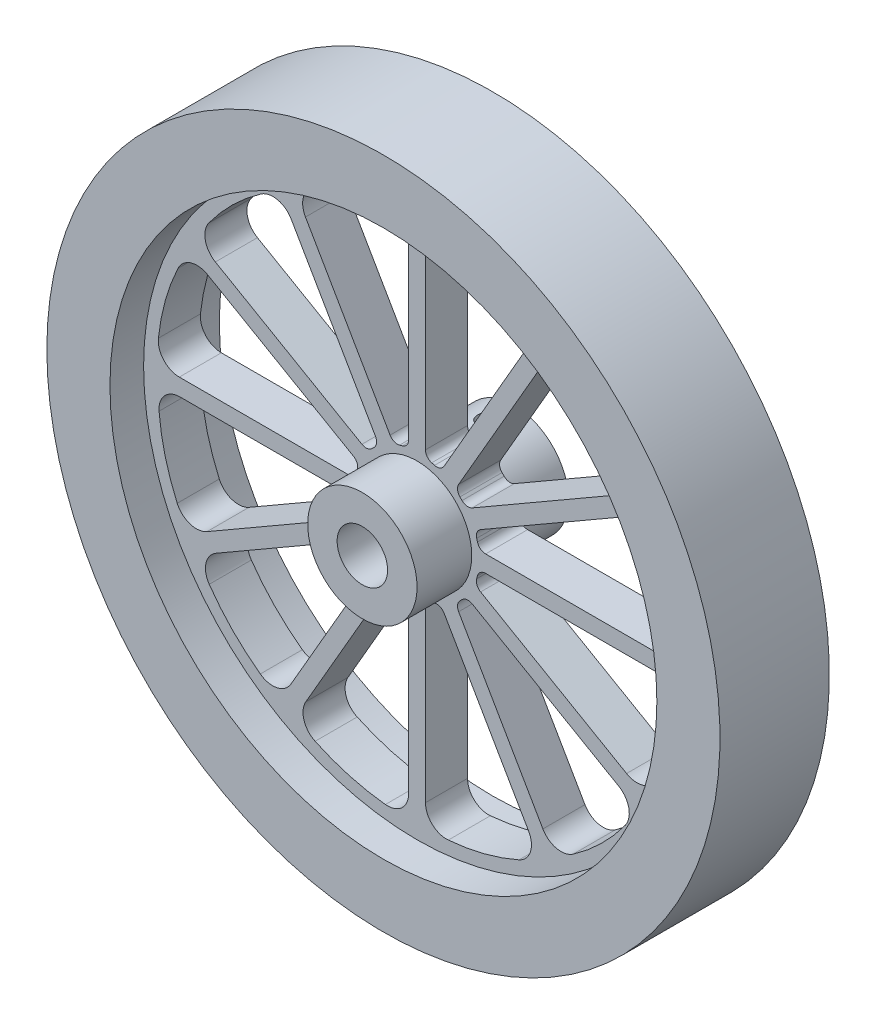
SolidWorks part; units mm, degrees
ref_plane "Front Plane" through (0, 0, 0) normal (0, 0, 1) x (1, 0, 0)
ref_plane "Top Plane" through (0, 0, 0) normal (0, 1, 0) x (1, 0, 0)
ref_plane "Right Plane" through (0, 0, 0) normal (1, 0, 0) x (0, 0, -1)
sketch "Sketch1" plane through (0, 0, 0) normal (0, 0, 1) x (1, 0, 0)
  line L0 (0, 93.8626) -> (0, -13) construction
  line L1 (2, 16.2894) -> (2, 56.5143)
  line L2 (9.8767, 13.107) -> (29.9892, 47.9429)
  line L3 (9.6149, 12.6535) -> (9.8767, 13.107)
  line L4 (6.4126, 15.107) -> (26.4422, 49.7992)
  line L5 (10.1946, 10.6928) -> (10.6928, 10.1946)
  line L6 (13.107, 9.8767) -> (47.7992, 29.9063)
  line L7 (15.107, 6.4126) -> (49.9429, 26.5251)
  line L8 (14.1752, 4.1629) -> (14.3575, 3.4824)
  line L9 (16.2894, 2) -> (56.3484, 2)
  line L10 (16.2894, -2) -> (56.5143, -2)
  line L11 (14.3575, -3.4824) -> (14.1752, -4.1629)
  line L12 (15.107, -6.4126) -> (49.7992, -26.4422)
  line L13 (13.107, -9.8767) -> (47.9429, -29.9892)
  line L14 (10.6928, -10.1946) -> (10.1946, -10.6928)
  line L15 (9.8767, -13.107) -> (29.9063, -47.7992)
  line L16 (6.4126, -15.107) -> (26.5251, -49.9429)
  line L17 (4.1629, -14.1752) -> (3.4824, -14.3575)
  line L18 (2, -16.2894) -> (2, -56.3484)
  line L19 (-2, -16.2894) -> (-2, -56.5143)
  line L20 (-3.4824, -14.3575) -> (-4.1629, -14.1752)
  line L21 (0, -65) -> (0, -93.8626) construction
  line L22 (-6.4126, -15.107) -> (-26.4422, -49.7992)
  line L23 (-9.8767, -13.107) -> (-29.9892, -47.9429)
  line L24 (-10.1946, -10.6928) -> (-10.6928, -10.1946)
  line L25 (3.4824, 14.3575) -> (4.1629, 14.1752)
  line L26 (-13.107, -9.8767) -> (-47.7992, -29.9063)
  line L27 (-15.107, -6.4126) -> (-49.9429, -26.5251)
  line L28 (-14.1752, -4.1629) -> (-14.3575, -3.4824)
  line L29 (-16.2894, -2) -> (-56.3484, -2)
  line L30 (-16.2894, 2) -> (-56.5143, 2)
  line L31 (-14.3575, 3.4824) -> (-14.1752, 4.1629)
  line L32 (-15.107, 6.4126) -> (-49.7992, 26.4422)
  line L33 (-13.107, 9.8767) -> (-47.9429, 29.9892)
  line L34 (-10.6928, 10.1946) -> (-10.1946, 10.6928)
  line L35 (-9.8767, 13.107) -> (-29.9063, 47.7992)
  line L36 (-6.4126, 15.107) -> (-26.5251, 49.9429)
  line L37 (-4.1629, 14.1752) -> (-3.4824, 14.3575)
  line L38 (-2, 16.2894) -> (-2, 56.3484)
  line L39 (0, 0) -> (2, 9.3915) construction
  circle A0 centre (0, 0) radius 65
  circle A1 centre (0, 0) radius 80
  circle A2 centre (0, 0) radius 6
  circle A3 centre (0, 0) radius 13
  arc A4 (7.5276, 61.4864) -> (24.2341, 56.8265) centre (2, 9.3915) cw
  arc A6 (26.4422, 49.7992) -> (24.2341, 56.8265) centre (22.112, 52.2992) ccw
  arc A7 (2, 56.5143) -> (7.5276, 61.4864) centre (7, 56.5143) cw
  arc A9 (6.4126, 15.107) -> (4.1629, 14.1752) centre (4.6806, 16.107) cw
  arc A10 (2, 16.2894) -> (3.4824, 14.3575) centre (4, 16.2894) ccw
  arc A11 (9.8767, 13.107) -> (10.1946, 10.6928) centre (11.6088, 12.107) ccw
  arc A12 (13.107, 9.8767) -> (10.6928, 10.1946) centre (12.107, 11.6088) cw
  arc A13 (47.7992, 29.9063) -> (49.4006, 37.0961) centre (45.2992, 34.2364) ccw
  arc A14 (37.2623, 49.485) -> (49.4006, 37.0961) centre (6.4278, 7.1333) cw
  arc A15 (29.9892, 47.9429) -> (37.2623, 49.485) centre (34.3193, 45.4429) cw
  arc A16 (15.107, 6.4126) -> (14.1752, 4.1629) centre (16.107, 4.6806) ccw
  arc A17 (16.2894, 2) -> (14.3575, 3.4824) centre (16.2894, 4) cw
  arc A18 (56.3484, 2) -> (61.3303, 7.4259) centre (56.3484, 7) ccw
  arc A19 (57.0126, 24.2242) -> (61.3303, 7.4259) centre (9.1333, 2.9637) cw
  arc A20 (49.9429, 26.5251) -> (57.0126, 24.2242) centre (52.4429, 22.195) cw
  arc A21 (16.2894, -2) -> (14.3575, -3.4824) centre (16.2894, -4) ccw
  arc A22 (15.107, -6.4126) -> (14.1752, -4.1629) centre (16.107, -4.6806) cw
  arc A23 (49.7992, -26.4422) -> (56.8265, -24.2341) centre (52.2992, -22.112) ccw
  arc A24 (61.4864, -7.5276) -> (56.8265, -24.2341) centre (9.3915, -2) cw
  arc A25 (56.5143, -2) -> (61.4864, -7.5276) centre (56.5143, -7) cw
  arc A26 (13.107, -9.8767) -> (10.6928, -10.1946) centre (12.107, -11.6088) ccw
  arc A27 (9.8767, -13.107) -> (10.1946, -10.6928) centre (11.6088, -12.107) cw
  arc A28 (29.9063, -47.7992) -> (37.0961, -49.4006) centre (34.2364, -45.2992) ccw
  arc A29 (49.485, -37.2623) -> (37.0961, -49.4006) centre (7.1333, -6.4278) cw
  arc A30 (47.9429, -29.9892) -> (49.485, -37.2623) centre (45.4429, -34.3193) cw
  arc A31 (6.4126, -15.107) -> (4.1629, -14.1752) centre (4.6806, -16.107) ccw
  arc A32 (2, -16.2894) -> (3.4824, -14.3575) centre (4, -16.2894) cw
  arc A33 (2, -56.3484) -> (7.4259, -61.3303) centre (7, -56.3484) ccw
  arc A34 (24.2242, -57.0126) -> (7.4259, -61.3303) centre (2.9637, -9.1333) cw
  arc A35 (26.5251, -49.9429) -> (24.2242, -57.0126) centre (22.195, -52.4429) cw
  arc A36 (-2, -16.2894) -> (-3.4824, -14.3575) centre (-4, -16.2894) ccw
  arc A37 (-6.4126, -15.107) -> (-4.1629, -14.1752) centre (-4.6806, -16.107) cw
  arc A38 (-26.4422, -49.7992) -> (-24.2341, -56.8265) centre (-22.112, -52.2992) ccw
  arc A39 (-7.5276, -61.4864) -> (-24.2341, -56.8265) centre (-2, -9.3915) cw
  arc A40 (-2, -56.5143) -> (-7.5276, -61.4864) centre (-7, -56.5143) cw
  arc A41 (-9.8767, -13.107) -> (-10.1946, -10.6928) centre (-11.6088, -12.107) ccw
  arc A42 (-13.107, -9.8767) -> (-10.6928, -10.1946) centre (-12.107, -11.6088) cw
  arc A43 (-47.7992, -29.9063) -> (-49.4006, -37.0961) centre (-45.2992, -34.2364) ccw
  arc A44 (-37.2623, -49.485) -> (-49.4006, -37.0961) centre (-6.4278, -7.1333) cw
  arc A45 (-29.9892, -47.9429) -> (-37.2623, -49.485) centre (-34.3193, -45.4429) cw
  arc A46 (-15.107, -6.4126) -> (-14.1752, -4.1629) centre (-16.107, -4.6806) ccw
  arc A47 (-16.2894, -2) -> (-14.3575, -3.4824) centre (-16.2894, -4) cw
  arc A48 (-56.3484, -2) -> (-61.3303, -7.4259) centre (-56.3484, -7) ccw
  arc A49 (-57.0126, -24.2242) -> (-61.3303, -7.4259) centre (-9.1333, -2.9637) cw
  arc A50 (-49.9429, -26.5251) -> (-57.0126, -24.2242) centre (-52.4429, -22.195) cw
  arc A51 (-16.2894, 2) -> (-14.3575, 3.4824) centre (-16.2894, 4) ccw
  arc A52 (-15.107, 6.4126) -> (-14.1752, 4.1629) centre (-16.107, 4.6806) cw
  arc A53 (-49.7992, 26.4422) -> (-56.8265, 24.2341) centre (-52.2992, 22.112) ccw
  arc A54 (-61.4864, 7.5276) -> (-56.8265, 24.2341) centre (-9.3915, 2) cw
  arc A55 (-56.5143, 2) -> (-61.4864, 7.5276) centre (-56.5143, 7) cw
  arc A56 (-13.107, 9.8767) -> (-10.6928, 10.1946) centre (-12.107, 11.6088) ccw
  arc A57 (-9.8767, 13.107) -> (-10.1946, 10.6928) centre (-11.6088, 12.107) cw
  arc A58 (-29.9063, 47.7992) -> (-37.0961, 49.4006) centre (-34.2364, 45.2992) ccw
  arc A59 (-49.485, 37.2623) -> (-37.0961, 49.4006) centre (-7.1333, 6.4278) cw
  arc A60 (-47.9429, 29.9892) -> (-49.485, 37.2623) centre (-45.4429, 34.3193) cw
  arc A61 (-6.4126, 15.107) -> (-4.1629, 14.1752) centre (-4.6806, 16.107) ccw
  arc A62 (-2, 16.2894) -> (-3.4824, 14.3575) centre (-4, 16.2894) cw
  arc A63 (-2, 56.3484) -> (-7.4259, 61.3303) centre (-7, 56.3484) ccw
  arc A64 (-24.2242, 57.0126) -> (-7.4259, 61.3303) centre (-2.9637, 9.1333) cw
  arc A65 (-26.5251, 49.9429) -> (-24.2242, 57.0126) centre (-22.195, 52.4429) cw
  point P65 (2, 61.7789)
  point P67 (2, 14.7547)
  dimension "D1" = 160
  dimension "D2" = 130
  dimension "D3" = 12
  dimension "D4" = 26
  dimension "D7" = 5
  dimension "D8" = 5
  dimension "D9" = 2
  dimension "D10" = 2
  dimension "D5" = 12
  dimension "D12" = 52.3873
  dimension "D6" = 2
  dimension "D13" = 2
  dimension "D14" = 3.4824
  dimension "D15" = 4.1629
  dimension "D16" = 22.112
  dimension "D11" = 9.6021
extrude "Boss-Extrude1" add sketch "Sketch1" along normal mid plane 26 contours A1 A0 region at (-77.7373, 0, 0)
extrude "Boss-Extrude2" add sketch "Sketch1<4>" along normal mid plane 10 contours A0 A10 L1 A7 A4 A6 L4 A9 L25 A3 L2 A15 A14 A13 L6 A12 L5 A11 L7 A20 A19 A18 L9 A17 L8 A16 L10 A25 A24 A23 L12 A22 L11 A21 L13 A30 A29 A28 L15 A27 L14 A26 region at (-63.1615, 0, 0)
sketch "Sketch1<4>" plane through (0, 0, 0) normal (0, 0, 1) x (1, 0, 0) same geometry as "Sketch1"
extrude "Boss-Extrude3" add sketch "Sketch1<5>" along normal mid plane 36 contours A3 A2 region at (-12.6323, 0, 0)
sketch "Sketch1<5>" plane through (0, 0, 0) normal (0, 0, 1) x (1, 0, 0) same geometry as "Sketch1"
sketch "Sketch3" plane through (0, 0, 0) normal (0, 1, 0) x (1, 0, 0)
  line L0 (13, 18) -> (-13, 18) construction
  circle A0 centre (0, 12) radius 2.5
  point P5 (0, 12)
  dimension "D2" = 5
  dimension "D1" = 6
extrude "Cut-Extrude1" cut sketch "Sketch3" against normal mid plane 36
